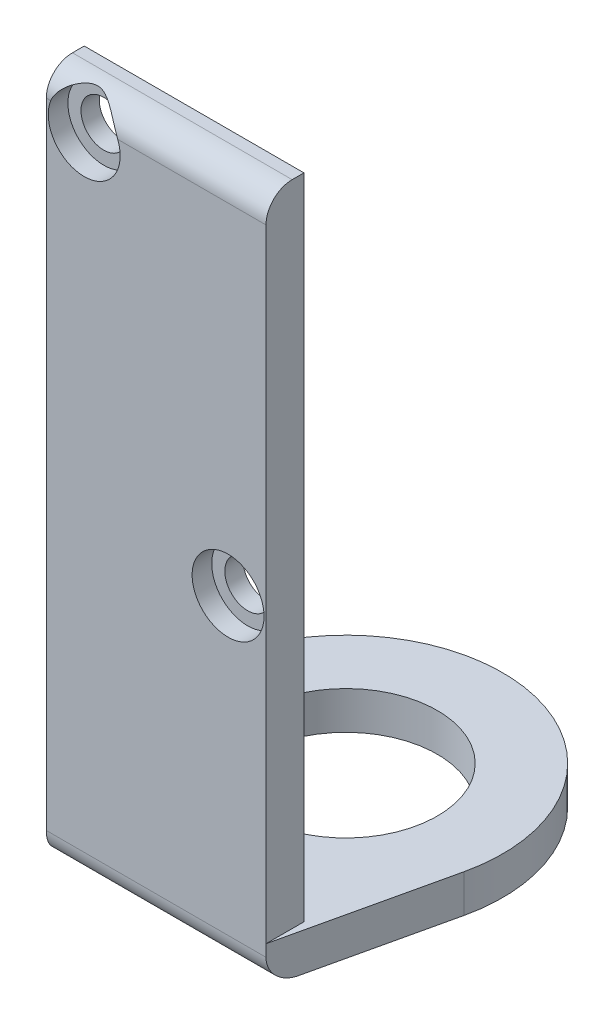
SolidWorks part; units mm, degrees
ref_plane "Alzado" through (0, 0, 0) normal (0, 0, 1) x (1, 0, 0)
ref_plane "Planta" through (0, 0, 0) normal (0, 1, 0) x (1, 0, 0)
ref_plane "Vista lateral" through (0, 0, 0) normal (1, 0, 0) x (0, 0, -1)
sketch "Croquis2" plane through (0, 33.2825, 0) normal (0, 1, 0) x (1, 0, 0)
  line L0 (2.7644, 0) -> (2.7644, -1) construction
  line L1 (19.7644, 0) -> (2.7644, 0) construction
  line L2 (19.7644, -1) -> (19.7644, 0) construction
  line L3 (2.7644, 0) -> (2.7644, -1) construction
  line L4 (19.7644, 0) -> (2.7644, 0) construction
  line L5 (19.7644, -1) -> (19.7644, 0) construction
  line L6 (19.6644, -1) -> (19.6644, -0.1)
  line L7 (19.6644, -0.1) -> (2.8644, -0.1)
  line L8 (2.8644, -0.1) -> (2.8644, -1)
  line L9 (2.8644, -1) -> (19.6644, -1) construction
  line L10 (2.7644, -3) -> (-2.7512, -3) construction
  line L11 (2.7644, -3) -> (-2.7512, -3) construction
  line L12 (2.8644, -1) -> (2.8644, -3)
  line L13 (19.6644, -1) -> (19.6644, -3)
  line L14 (19.6644, -3) -> (2.8644, -3)
  dimension "D1" = 0.1
extrude "Saliente-Extruir1" add sketch "Croquis2" against normal up to surface (52.5 mm away)
sketch "Croquis3" plane through (0, 0, 3) normal (0, 0, 1) x (1, 0, 0)
  circle A0 centre (5.7644, 30.2825) radius 1.45 construction
  circle A1 centre (16.7644, 5.2825) radius 1.45 construction
  circle A2 centre (5.7644, 30.2825) radius 1.45 construction
  circle A3 centre (16.7644, 5.2825) radius 1.45 construction
  circle A4 centre (5.7644, 30.2825) radius 1.75
  circle A5 centre (16.7644, 5.2825) radius 1.75
  dimension "D1" = 3.5
  dimension "D2" = 3.5
extrude "Cortar-Extruir3" cut sketch "Croquis3" against normal up to next
sketch "Croquis4" plane through (0, 0, 3) normal (0, 0, 1) x (1, 0, 0)
  circle A0 centre (5.7644, 30.2825) radius 2.75
  circle A1 centre (16.7644, 5.2825) radius 2.75
  dimension "D1" = 5.5
  dimension "D2" = 5.5
extrude "Cortar-Extruir4" cut sketch "Croquis4" against normal blind 1.5
sketch "Croquis5" plane through (0, -19.2175, 0) normal (0, 1, 0) x (1, 0, 0)
  line L0 (2.8644, -3) -> (19.6644, -3) construction
  line L1 (2.8644, -3) -> (19.6644, -3)
  line L2 (19.6644, -3) -> (22.4666, 9.3433)
  line L3 (2.8644, -3) -> (-0.6937, 8.4346)
  circle A0 centre (10.7644, 12) radius 7 construction
  circle A1 centre (10.7644, 12) radius 12 construction
  circle A2 centre (10.7644, 12) radius 7 construction
  circle A3 centre (10.7644, 12) radius 12 construction
  circle A4 centre (10.7644, 12) radius 7
  arc A5 (-0.6937, 8.4346) -> (22.4666, 9.3433) centre (10.7644, 12) cw
  dimension "D1" = 14
  dimension "D2" = 12
extrude "Saliente-Extruir2" add sketch "Croquis5" along normal blind 2.9
fillet "Redondeo1" radius 2 2 edges at (11.2644, 33.2825, 3) (11.2644, -19.2175, 3)
equation "\"D2@Croquis3\"= \"D1@Croquis3\""
equation "\"D2@Croquis4\"= \"D1@Croquis4\""
